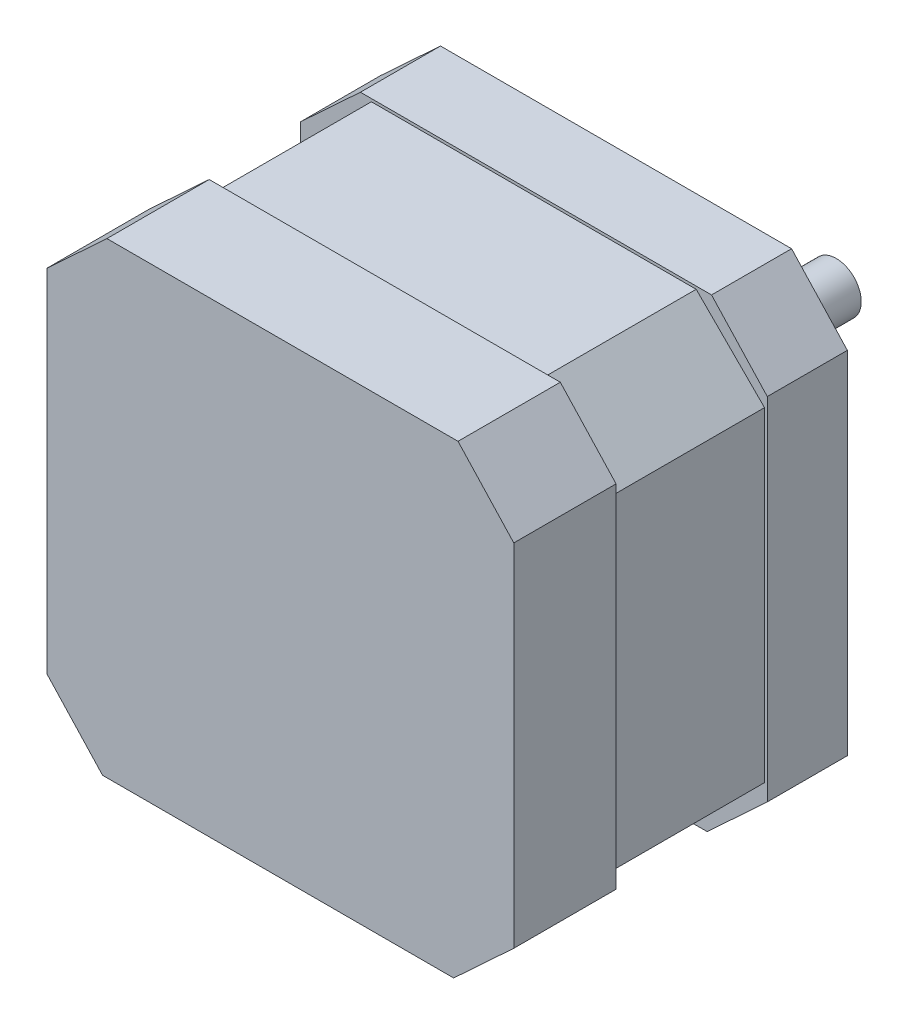
SolidWorks part; units mm, degrees
material "Ferro dúctil"
ref_plane "Plano frontal" through (0, 0, 0) normal (0, 0, 1) x (1, 0, 0)
ref_plane "Plano superior" through (0, 0, 0) normal (0, 1, 0) x (1, 0, 0)
ref_plane "Plano direito" through (0, 0, 0) normal (1, 0, 0) x (0, 0, -1)
sketch "Esboço1" plane through (0, 0, 0) normal (0, 0, 1) x (1, 0, 0)
  line L0 (-1.3818, -36.7436) -> (-36.7436, 1.3818)
  line L1 (-21, 21) -> (21, 21)
  line L2 (-21, 21) -> (-21, -21)
  line L3 (-21, -21) -> (21, -21)
  line L4 (21, 21) -> (21, -21)
  line L5 (-21, 21) -> (21, -21) construction
  line L6 (-21, -21) -> (21, 21) construction
  line L7 (-1.3818, -36.7436) -> (36.7436, -1.3818)
  line L8 (-36.7436, 1.3818) -> (1.3818, 36.7436)
  line L9 (36.7436, -1.3818) -> (1.3818, 36.7436)
  line L10 (-1.3818, -36.7436) -> (1.3818, 36.7436) construction
  line L11 (-36.7436, 1.3818) -> (36.7436, -1.3818) construction
  point P0 (0, 0)
  point P7 (0, 0)
  dimension "D1" = 42
  dimension "D2" = 52
extrude "Ressalto-extrusão1" add sketch "Esboço1" along normal blind 30 contours L4 L9 L1 L8 L2 L0 L3 L7 region at (0, 0, 0)
sketch "Esboço2" plane through (0, 0, 30) normal (0, 0, 1) x (1, 0, 0)
  line L1 (-20.75, -20.75) -> (20.75, -20.75)
  line L2 (-20.75, -20.75) -> (-20.75, 20.75)
  line L3 (-20.75, 20.75) -> (20.75, 20.75)
  line L4 (20.75, -20.75) -> (20.75, 20.75)
  line L5 (-20.75, -20.75) -> (20.75, 20.75) construction
  line L6 (-20.75, 20.75) -> (20.75, -20.75) construction
  line L7 (0, -35.3553) -> (-35.3553, 0)
  line L8 (0, -35.3553) -> (35.3553, 0)
  line L9 (-35.3553, 0) -> (0, 35.3553)
  line L10 (35.3553, 0) -> (0, 35.3553)
  line L11 (0, -35.3553) -> (0, 35.3553) construction
  line L12 (-35.3553, 0) -> (35.3553, 0) construction
  point P0 (0, 0)
  point P8 (-17.6777, 17.6777)
  point P9 (0, 0)
  dimension "D1" = 50
  dimension "D2" = 41.5
extrude "Corte-Extrusão-Fina1" cut sketch "Esboço2" against normal offset from surface (13.6 mm away) 7.2 from offset 9.2 thin contours L4 L10 L3 L9 L2 L7 L1 L8 up to face at (0, 0, 0) offset against normal yes thin type one direction wall 10
sketch "Esboço3" plane through (0, 0, 0) normal (0, 0, -1) x (-1, 0, 0)
  circle A0 centre (0, 0) radius 2.25
  dimension "D1" = 4.5
extrude "Ressalto-extrusão2" add sketch "Esboço3" along normal blind 20
sketch "Esboço4" plane through (0, 0, 0) normal (0, 0, -1) x (-1, 0, 0)
  circle A0 centre (0, 0) radius 10
  dimension "D1" = 20
extrude "Ressalto-extrusão3" add sketch "Esboço4" along normal blind 2
sketch "Esboço5" plane through (0, 0, 0) normal (0, 0, -1) x (-1, 0, 0)
  line L1 (15.5, 15.5) -> (-15.5, 15.5) construction
  line L2 (15.5, 15.5) -> (15.5, -15.5) construction
  line L3 (15.5, -15.5) -> (-15.5, -15.5) construction
  line L4 (-15.5, 15.5) -> (-15.5, -15.5) construction
  line L5 (15.5, 15.5) -> (-15.5, -15.5) construction
  line L6 (15.5, -15.5) -> (-15.5, 15.5) construction
  circle A0 centre (15.5, -15.5) radius 1.5
  circle A1 centre (-15.5, -15.5) radius 1.5
  circle A2 centre (-15.5, 15.5) radius 1.5
  circle A3 centre (15.5, 15.5) radius 1.5
  point P0 (0, 0)
  dimension "D1" = 3
  dimension "D2" = 31
extrude "Corte-extrusão1" cut sketch "Esboço5" against normal blind 10
